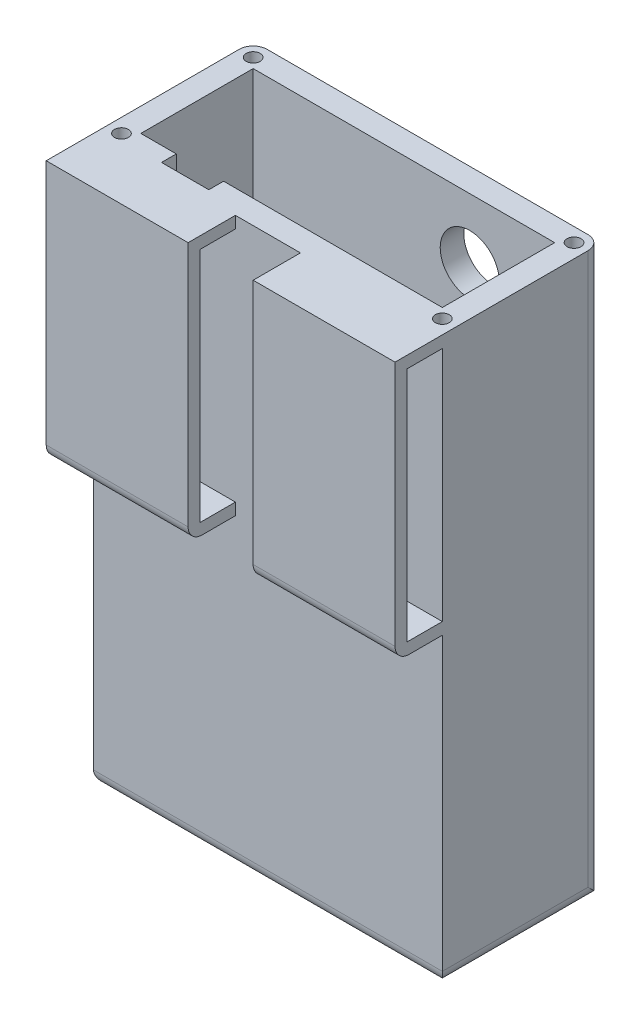
SolidWorks part; units mm, degrees
ref_plane "Front Plane" through (0, 0, 0) normal (0, 0, 1) x (1, 0, 0)
ref_plane "Top Plane" through (0, 0, 0) normal (0, 1, 0) x (1, 0, 0)
ref_plane "Right Plane" through (0, 0, 0) normal (1, 0, 0) x (0, 0, -1)
sketch "Sketch1" plane through (0, 0, 0) normal (0, 1, 0) x (1, 0, 0)
  line L1 (0, 0) -> (74.93, 0)
  line L2 (0, 0) -> (0, 34.29)
  line L3 (0, 34.29) -> (74.93, 34.29)
  line L4 (74.93, 0) -> (74.93, 34.29)
  dimension "D1" = 74.93
  dimension "D2" = 34.29
extrude "Boss-Extrude1" add sketch "Sketch1" along normal blind 87.122
shell "Shell1" thickness 2.54 removed face at (37.465, 43.561, -34.29)
sketch "Sketch12" plane through (0, 87.122, 0) normal (0, 1, 0) x (1, 0, 0)
  line L1 (0, 0) -> (74.93, 0)
  line L2 (0, 0) -> (0, 34.29)
  line L3 (0, 34.29) -> (74.93, 34.29)
  line L4 (74.93, 0) -> (74.93, 34.29)
extrude "Boss-Extrude6" add sketch "Sketch12" along normal blind 34.29
shell "Shell2" thickness 5.08 removed face at (37.465, 121.412, -17.145)
sketch "Sketch18" plane through (0, 89.662, 0) normal (0, 1, 0) x (1, 0, 0)
  line L0 (5.08, 5.08) -> (69.85, 5.08) construction
  line L1 (34.925, 5.08) -> (22.225, 5.08)
  line L2 (34.925, 5.08) -> (34.925, 14.605)
  line L3 (34.925, 14.605) -> (22.225, 14.605)
  line L4 (22.225, 5.08) -> (22.225, 14.605)
  line L5 (69.85, 5.08) -> (69.85, 29.21) construction
  line L6 (69.85, 29.21) -> (5.08, 29.21) construction
  line L7 (69.85, 22.21) -> (64.85, 22.21)
  line L8 (69.85, 22.21) -> (69.85, 12.08)
  line L9 (69.85, 12.08) -> (64.85, 12.08)
  line L10 (64.85, 22.21) -> (64.85, 12.08)
  dimension "D1" = 34.925
  dimension "D2" = 47.625
  dimension "D3" = 9.525
  dimension "D4" = 5
  dimension "D5" = 7
  dimension "D6" = 7
extrude "Cut-Extrude13" cut sketch "Sketch18" against normal up to next
sketch "Sketch20" plane through (0, 121.412, 0) normal (0, 1, 0) x (1, 0, 0)
  line L0 (0, 34.29) -> (0, 0) construction
  line L2 (74.93, 34.29) -> (0, 34.29) construction
  line L3 (0, 0) -> (74.93, 0) construction
  line L4 (74.93, 0) -> (74.93, 34.29) construction
  circle A0 centre (3, 31.29) radius 1.5
  circle A1 centre (3, 3) radius 1.5
  circle A2 centre (71.93, 3) radius 1.5
  circle A3 centre (71.93, 31.29) radius 1.5
  dimension "D1" = 3
  dimension "D2" = 3
  dimension "D3" = 3
  dimension "D4" = 3
  dimension "D5" = 3
  dimension "D6" = 3
  dimension "D7" = 3
  dimension "D8" = 3
extrude "Cut-Extrude14" cut sketch "Sketch20" against normal blind 20
sketch "Sketch15" plane through (0, 0, 0) normal (0, 0, 1) x (1, 0, 0)
  line L1 (0, 121.412) -> (30.48, 121.412)
  line L2 (0, 121.412) -> (0, 65.532)
  line L3 (0, 65.532) -> (30.48, 65.532)
  line L4 (30.48, 121.412) -> (30.48, 65.532)
  line L5 (74.93, 121.412) -> (44.45, 121.412)
  line L6 (74.93, 121.412) -> (74.93, 65.532)
  line L7 (74.93, 65.532) -> (44.45, 65.532)
  line L8 (44.45, 121.412) -> (44.45, 65.532)
  dimension "D1" = 30.48
  dimension "D2" = 30.48
  dimension "D3" = 55.88
  dimension "D4" = 55.88
extrude "Boss-Extrude8" add sketch "Sketch15" along normal blind 10.16
sketch "Sketch16" plane through (0, 0, 0) normal (-1, 0, 0) x (0, 0, 1)
  line L0 (10.16, 121.412) -> (10.16, 65.532) construction
  line L1 (7.62, 68.072) -> (0, 68.072)
  line L2 (7.62, 68.072) -> (7.62, 118.872)
  line L3 (7.62, 118.872) -> (0, 118.872)
  line L4 (0, 68.072) -> (0, 118.872)
  line L5 (10.16, 65.532) -> (0, 65.532) construction
  line L6 (-34.29, 121.412) -> (10.16, 121.412) construction
  line L8 (0, 65.532) -> (0, 0) construction
  dimension "D1" = 2.54
  dimension "D2" = 2.54
  dimension "D3" = 2.54
extrude "Cut-Extrude11" cut sketch "Sketch16" against normal through all
fillet "Fillet1" radius 3 7 edges at (59.69, 65.532, 10.16) (15.24, 65.532, 10.16) (74.93, 0, -17.145) (0, 0, -17.145) (37.465, 0, 0) (74.93, 60.706, -34.29) (0, 60.706, -34.29)
sketch "Sketch21" plane through (0, 121.412, 0) normal (0, 1, 0) x (1, 0, 0)
  line L0 (5.08, 5.08) -> (69.85, 5.08) construction
  line L1 (12.7, 5.08) -> (22.86, 5.08)
  line L2 (12.7, 5.08) -> (12.7, 1.905)
  line L3 (12.7, 1.905) -> (22.86, 1.905)
  line L4 (22.86, 5.08) -> (22.86, 1.905)
  line L5 (5.08, 29.21) -> (5.08, 5.08) construction
  dimension "D1" = 10.16
  dimension "D2" = 3.175
  dimension "D3" = 7.62
extrude "Cut-Extrude15" cut sketch "Sketch21" against normal blind 31.75
sketch "Sketch22" plane through (0, 0, -34.29) normal (0, 0, -1) x (-1, 0, 0)
  line L0 (-71.93, 121.412) -> (-3, 121.412) construction
  line L1 (-71.93, 121.412) -> (-71.93, 84.582) construction
  circle A0 centre (-51.61, 108.204) radius 6.35
  dimension "D1" = 12.7
  dimension "D2" = 13.208
  dimension "D3" = 20.32
extrude "Cut-Extrude16" cut sketch "Sketch22" against normal up to next
